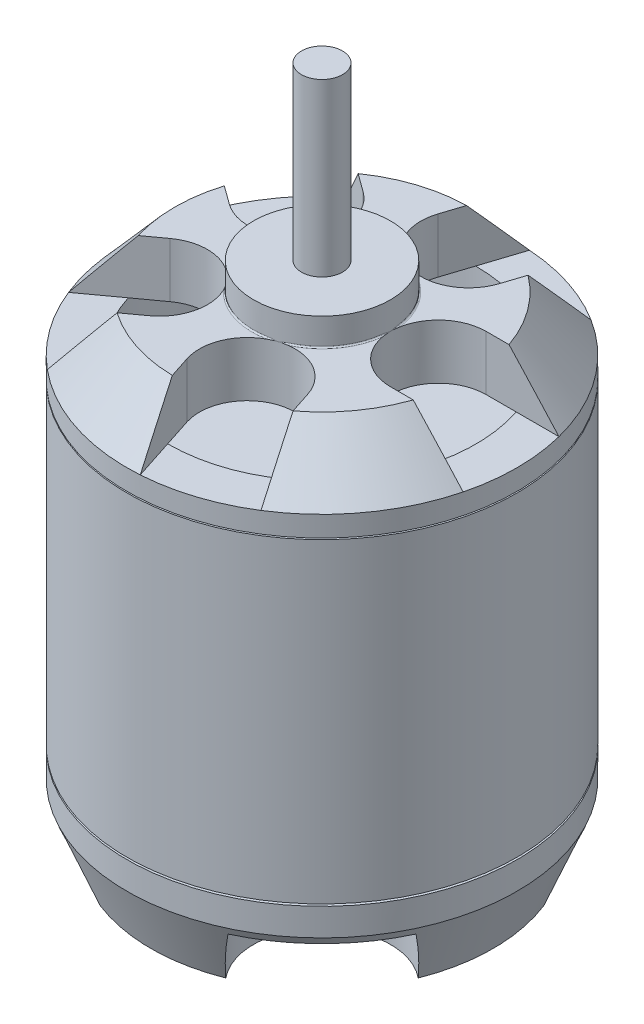
SolidWorks part; units mm, degrees
ref_plane "Front Plane" through (0, 0, 0) normal (0, 0, 1) x (1, 0, 0)
ref_plane "Top Plane" through (0, 0, 0) normal (0, 1, 0) x (1, 0, 0)
ref_plane "Right Plane" through (0, 0, 0) normal (1, 0, 0) x (0, 0, -1)
sketch "Sketch1" plane through (0, 0, 0) normal (0, 1, 0) x (1, 0, 0)
  circle A0 centre (0, 0) radius 14.25
  dimension "D1" = 28.5
extrude "Boss-Extrude1" add sketch "Sketch1" along normal blind 35.3
sketch "Sketch2" plane through (0, 35.3, 0) normal (0, 1, 0) x (1, 0, 0)
  circle A0 centre (0, 0) radius 5
  dimension "D1" = 10
extrude "Boss-Extrude2" add sketch "Sketch2" along normal blind 2
ref_plane "Plane1" through (0, 49.8, 0) normal (0, 1, 0) x (1, 0, 0)
sketch "Sketch4" plane through (0, 0, 0) normal (0, 0, 1) x (1, 0, 0)
  line L0 (14.25, 0) -> (14.25, 4.5)
  line L1 (14.25, 4.5) -> (12.5, 0)
  line L2 (-14.25, 0) -> (14.25, 0) construction
  line L3 (12.5, 0) -> (14.25, 0)
  line L4 (10.75, 35.3) -> (14.25, 35.3)
  line L5 (14.25, 35.3) -> (-14.25, 35.3) construction
  line L6 (14.25, 35.3) -> (14.25, 31.3)
  line L7 (14.25, 0) -> (14.25, 35.3) construction
  line L8 (14.25, 31.3) -> (10.75, 35.3)
  line L9 (0, 21.4572) -> (0, 31.3) construction
  dimension "D1" = 4.5
  dimension "D2" = 12.5
  dimension "D3" = 4
  dimension "D4" = 3.5
revolve "Cut-Revolve1" cut sketch "Sketch4" angle 360 about L9
sketch "Sketch5" plane through (0, 0, 0) normal (0, 0, 1) x (1, 0, 0)
  line L0 (14.25, 4.5) -> (14.25, 31.3) construction
  line L1 (14.25, 6.65) -> (14, 6.65)
  line L2 (14.25, 6.65) -> (14.25, 6.5)
  line L3 (14.25, 6.5) -> (14, 6.5)
  line L4 (14, 6.65) -> (14, 6.5)
  line L5 (14.25, 4.5) -> (-14.25, 4.5) construction
  line L6 (0, 12.7835) -> (0, 25.6712) construction
  line L7 (14.25, 31.3) -> (-14.25, 31.3) construction
  line L8 (14.25, 29.8) -> (14, 29.8)
  line L9 (14.25, 29.8) -> (14.25, 29.7)
  line L10 (14.25, 29.7) -> (14, 29.7)
  line L11 (14, 29.8) -> (14, 29.7)
  dimension "D1" = 0.15
  dimension "D2" = 0.25
  dimension "D3" = 2
  dimension "D4" = 0.1
  dimension "D5" = 1.5
  dimension "D6" = 0.25
revolve "Cut-Revolve2" cut sketch "Sketch5" angle 360 about L6
sketch "Sketch6" plane through (0, 0, 0) normal (0, -1, 0) x (1, 0, 0)
  circle A0 centre (0, 0) radius 4
  dimension "D1" = 8
extrude "Cut-Extrude1" cut sketch "Sketch6" against normal blind 1.5
chamfer "Chamfer1" distance 1.5 angle 45 1 edges at (0, 0, -4)
sketch "Sketch7" plane through (0, 35.3, 0) normal (0, 1, 0) x (1, 0, 0)
  line L0 (8.5, 3.5) -> (13.8135, 3.5)
  line L1 (8.5, -3.5) -> (13.8135, -3.5)
  line L2 (5.9553, -7.0024) -> (7.5973, -12.0558)
  line L3 (-0.7021, -9.1655) -> (0.9399, -14.219)
  line L4 (-4.8194, -7.8277) -> (-9.1181, -10.9509)
  line L5 (-8.9339, -2.1646) -> (-13.2326, -5.2878)
  line L6 (-8.9339, 2.1646) -> (-13.2326, 5.2878)
  line L7 (-4.8194, 7.8277) -> (-9.1181, 10.9509)
  line L8 (-0.7021, 9.1655) -> (0.9399, 14.219)
  line L9 (5.9553, 7.0024) -> (7.5973, 12.0558)
  arc A0 (8.5, 3.5) -> (8.5, -3.5) centre (8.5, 0) ccw
  circle A1 centre (0, 0) radius 14.25 construction
  arc A2 (13.8135, -3.5) -> (13.8135, 3.5) centre (0, 0) ccw
  circle A3 centre (0, 0) radius 5 construction
  arc A4 (5.9553, -7.0024) -> (-0.7021, -9.1655) centre (2.6266, -8.084) ccw
  arc A5 (0.9399, -14.219) -> (7.5973, -12.0558) centre (0, 0) ccw
  arc A6 (-4.8194, -7.8277) -> (-8.9339, -2.1646) centre (-6.8766, -4.9962) ccw
  arc A7 (-13.2326, -5.2878) -> (-9.1181, -10.9509) centre (0, 0) ccw
  arc A8 (-8.9339, 2.1646) -> (-4.8194, 7.8277) centre (-6.8766, 4.9962) ccw
  arc A9 (-9.1181, 10.9509) -> (-13.2326, 5.2878) centre (0, 0) ccw
  arc A10 (-0.7021, 9.1655) -> (5.9553, 7.0024) centre (2.6266, 8.084) ccw
  arc A11 (7.5973, 12.0558) -> (0.9399, 14.219) centre (0, 0) ccw
  point P34 (0, 0)
  dimension "D1" = 7
  dimension "D2" = 5
extrude "Cut-Extrude2" cut sketch "Sketch7" against normal blind 4
sketch "Sketch8" plane through (0, 31.3, 0) normal (0, 1, 0) x (1, 0, 0)
  circle A0 centre (0, 0) radius 11.25
  arc A1 (13.8135, 3.5) -> (7.5973, 12.0558) centre (0, 0) ccw construction
  dimension "D1" = 3
extrude "Cut-Extrude3" cut sketch "Sketch8" against normal blind 4
fillet "Fillet1" radius 0.1 5 edges at (4.0451, 35.3, -2.9389) (-1.5451, 35.3, -4.7553) (-5, 35.3, 0) (-1.5451, 35.3, 4.7553) (4.0451, 35.3, 2.9389)
sketch "Sketch9" plane through (0, 0, 0) normal (0, -1, 0) x (1, 0, 0)
  circle A0 centre (-8, 0) radius 1.5
  circle A1 centre (8, 0) radius 1.5
  circle A2 centre (0, 9.5) radius 1.5
  circle A3 centre (0, -9.5) radius 1.5
  dimension "D3" = 3
  dimension "D4" = 3
  dimension "D5" = 3
  dimension "D6" = 3
  dimension "D1" = 8
  dimension "D2" = 8
  dimension "D7" = 9.5
  dimension "D8" = 9.5
extrude "Cut-Extrude4" cut sketch "Sketch9" against normal blind 4
thread "Thread1" pitch 0.5 start angle 0, offset 0, length 0, pitch 0.5, diameter 3
ref_plane "Plane2" through (1.5, 0, 9.5) normal (0, 0, 1) x (1, 0, 0)
sketch "Thread Profile1" plane through (1.5, 0, 9.5) normal (0, 0, 1) x (1, 0, 0)
  line L0 (0, 0) -> (0, 0.5) construction
  line L1 (0, 0) -> (0.2706, 0.1562)
  line L2 (0.2706, 0.1562) -> (0.2706, 0.2187)
  line L3 (0.2706, 0.2187) -> (0, 0.375)
  line L4 (0.2706, 0.1875) -> (0, 0.1875) construction
  line L11 (0, 0) -> (0, 0.375)
  point P2 (0, 0)
  dimension "Pitch" = 0.5
  dimension "Profile_Angle" = 60
  dimension "Profile_Land" = 0.0625
  dimension "Profile_Height" = 0.2706
thread "Thread2" pitch 0.5 profile "Thread Profile2" start angle 0, offset 0, length 0, pitch 0.5, diameter 3
ref_plane "Plane3" through (-6.5, 0, 0) normal (0, 0, 1) x (1, 0, 0)
sketch "Thread Profile2" plane through (-6.5, 0, 0) normal (0, 0, 1) x (1, 0, 0)
  line L0 (0, 0) -> (0, 0.5) construction
  line L1 (0, 0) -> (0.2706, 0.1562)
  line L2 (0.2706, 0.1562) -> (0.2706, 0.2187)
  line L3 (0.2706, 0.2187) -> (0, 0.375)
  line L4 (0.2706, 0.1875) -> (0, 0.1875) construction
  line L11 (0, 0) -> (0, 0.375)
  point P2 (0, 0)
  dimension "Pitch" = 0.5
  dimension "Profile_Angle" = 60
  dimension "Profile_Land" = 0.0625
  dimension "Profile_Height" = 0.2706
thread "Thread3" pitch 0.5 profile "Thread Profile3" start angle 0, offset 0, length 0, pitch 0.5, diameter 3
ref_plane "Plane4" through (1.5, 0, -9.5) normal (0, 0, 1) x (1, 0, 0)
sketch "Thread Profile3" plane through (1.5, 0, -9.5) normal (0, 0, 1) x (1, 0, 0)
  line L0 (0, 0) -> (0, 0.5) construction
  line L1 (0, 0) -> (0.2706, 0.1562)
  line L2 (0.2706, 0.1562) -> (0.2706, 0.2187)
  line L3 (0.2706, 0.2187) -> (0, 0.375)
  line L4 (0.2706, 0.1875) -> (0, 0.1875) construction
  line L11 (0, 0) -> (0, 0.375)
  point P2 (0, 0)
  dimension "Pitch" = 0.5
  dimension "Profile_Angle" = 60
  dimension "Profile_Land" = 0.0625
  dimension "Profile_Height" = 0.2706
thread "Thread4" pitch 0.5 profile "Thread Profile4" start angle 0, offset 0, length 0, pitch 0.5, diameter 3
ref_plane "Plane5" through (9.5, 0, 0) normal (0, 0, 1) x (1, 0, 0)
sketch "Thread Profile4" plane through (9.5, 0, 0) normal (0, 0, 1) x (1, 0, 0)
  line L0 (0, 0) -> (0, 0.5) construction
  line L1 (0, 0) -> (0.2706, 0.1562)
  line L2 (0.2706, 0.1562) -> (0.2706, 0.2187)
  line L3 (0.2706, 0.2187) -> (0, 0.375)
  line L4 (0.2706, 0.1875) -> (0, 0.1875) construction
  line L11 (0, 0) -> (0, 0.375)
  point P2 (0, 0)
  dimension "Pitch" = 0.5
  dimension "Profile_Angle" = 60
  dimension "Profile_Land" = 0.0625
  dimension "Profile_Height" = 0.2706
sketch "Sketch18" plane through (0, 0, 0) normal (0, -1, 0) x (1, 0, 0)
  line L0 (0, 0) -> (-13.6206, 13.6206) construction
  line L1 (0, 0) -> (-17.8145, 0) construction
  circle A0 centre (-8.4853, 8.4853) radius 5
  circle A1 centre (8.4853, 8.4853) radius 5
  circle A2 centre (8.4853, -8.4853) radius 5
  circle A3 centre (-8.4853, -8.4853) radius 5
  point P15 (0, 0)
  dimension "D2" = 10
  dimension "D1" = 45
  dimension "D3" = 12
  dimension "D4" = 4
extrude "Cut-Extrude5" cut sketch "Sketch18" against normal blind 4
sketch "Sketch19" plane through (0, 4, 0) normal (0, -1, 0) x (1, 0, 0)
  circle A0 centre (0, 0) radius 12.0556
  arc A1 (5.8927, -12.7606) -> (12.7606, -5.8927) centre (0, 0) ccw construction
  dimension "D1" = 2
extrude "Cut-Extrude6" cut sketch "Sketch19" against normal blind 4
sketch "Sketch3" plane through (0, 49.8, 0) normal (0, 1, 0) x (1, 0, 0)
  circle A0 centre (0, 0) radius 1.5
  dimension "D1" = 3
extrude "Boss-Extrude3" add sketch "Sketch3" against normal blind 52.3
